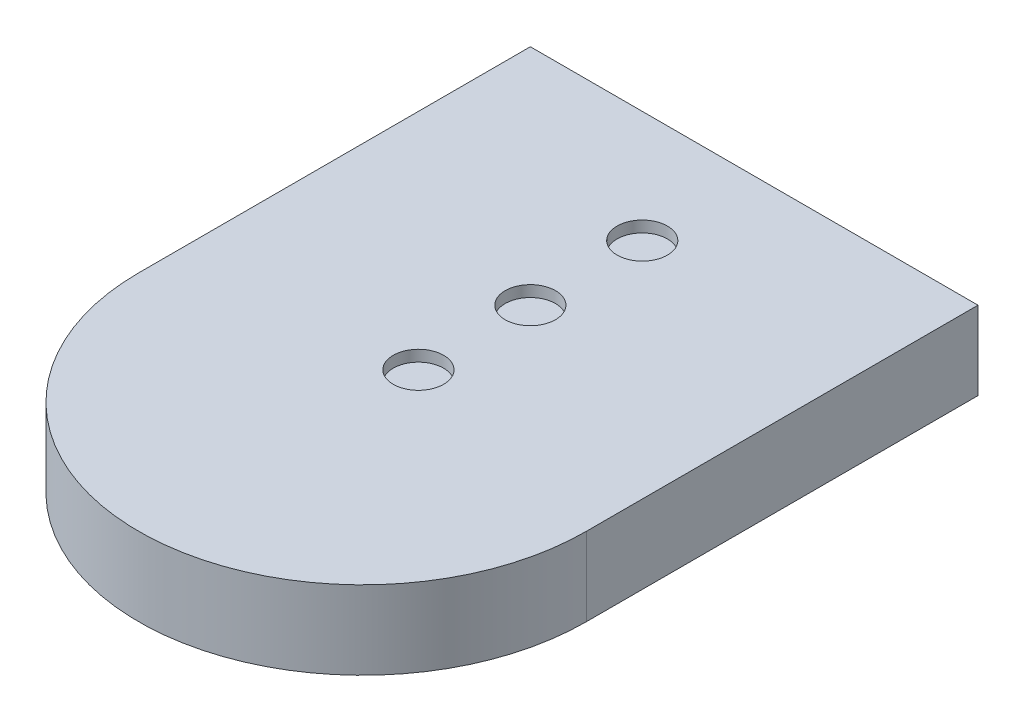
SolidWorks part; units mm, degrees
material "Rubber"
ref_plane "Front Plane" through (0, 0, 0) normal (0, 0, 1) x (1, 0, 0)
ref_plane "Top Plane" through (0, 0, 0) normal (0, 1, 0) x (1, 0, 0)
ref_plane "Right Plane" through (0, 0, 0) normal (1, 0, 0) x (0, 0, -1)
sketch "Sketch1" plane through (0, 0, 0) normal (0, 0, 1) x (1, 0, 0)
  line L0 (0, 0) -> (0, -7)
  line L4 (0, 0) -> (40, 0)
  line L5 (0, -7) -> (40, -7)
  line L6 (40, -7) -> (40, 0)
  dimension "D1" = 40
  dimension "D2" = 7
extrude "Boss-Extrude1" add sketch "Sketch1" along normal blind 55
sketch "Sketch2" plane through (0, 0, 0) normal (0, 1, 0) x (1, 0, 0)
  line L0 (40, 0) -> (0, 0) construction
  line L1 (40, -55) -> (40, 0) construction
  circle A0 centre (20, -10) radius 2.25
  circle A1 centre (20, -20) radius 2.25
  circle A2 centre (20, -30) radius 2.25
  dimension "D4" = 4.5
  dimension "D1" = 10
  dimension "D2" = 20
  dimension "D3" = 3
extrude "Cut-Extrude1" cut sketch "Sketch2" against normal blind 7
fillet "Fillet1" 2 edges at (40, -3.5, 55) (0, -3.5, 55) type full round first side face at (40, -3.5, 27.5) second side face at (0, -3.5, 27.5) middle face at (20, -3.5, 55)
sketch "Sketch4" plane through (0, 0, 0) normal (0, 0, -1) x (-1, 0, 0)
  line L0 (-40, 0) -> (0, 0) construction
  line L1 (-30, -1) -> (-10, -1)
  line L2 (-30, -1) -> (-30, -6)
  line L3 (-30, -6) -> (-10, -6)
  line L4 (-10, -1) -> (-10, -6)
  line L5 (-30, -1) -> (-10, -6) construction
  line L6 (-30, -6) -> (-10, -1) construction
  line L8 (0, 0) -> (0, -7) construction
  point P0 (-20, -3.5)
  dimension "D1" = 1
  dimension "D2" = 5
  dimension "D3" = 20
  dimension "D4" = 10
extrude "Cut-Extrude2" cut sketch "Sketch4" against normal blind 40
